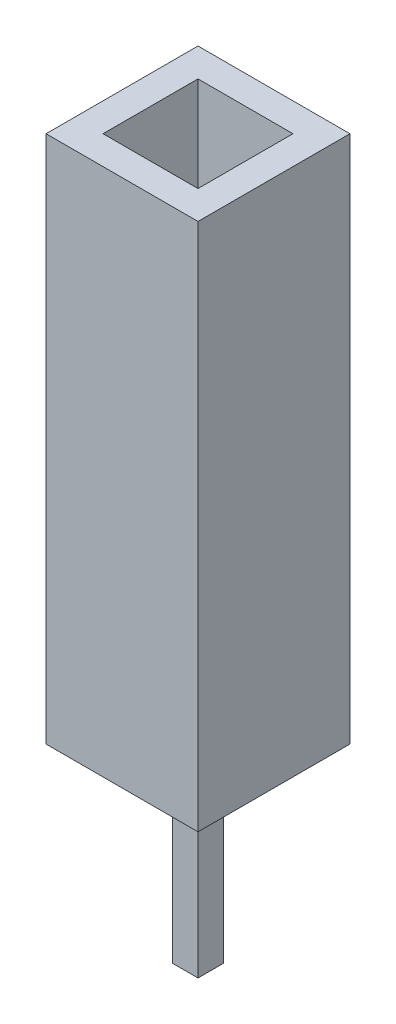
SolidWorks part; units mm, degrees
ref_plane "Front Plane" through (0, 0, 0) normal (0, 0, 1) x (1, 0, 0)
ref_plane "Top Plane" through (0, 0, 0) normal (0, 1, 0) x (1, 0, 0)
ref_plane "Right Plane" through (0, 0, 0) normal (1, 0, 0) x (0, 0, -1)
sketch "Sketch1" plane through (0, 0, 0) normal (0, 1, 0) x (1, 0, 0)
  line L1 (1.2, 1.2) -> (-1.2, 1.2)
  line L2 (1.2, 1.2) -> (1.2, -1.2)
  line L3 (1.2, -1.2) -> (-1.2, -1.2)
  line L4 (-1.2, 1.2) -> (-1.2, -1.2)
  line L5 (1.2, 1.2) -> (-1.2, -1.2) construction
  line L6 (1.2, -1.2) -> (-1.2, 1.2) construction
  point P0 (0, 0)
  dimension "D1" = 2.4
  dimension "D2" = 2.4
extrude "Boss-Extrude1" add sketch "Sketch1" along normal blind 8.35
sketch "Sketch2" plane through (0, 8.35, 0) normal (0, 1, 0) x (1, 0, 0)
  line L1 (-0.75, -0.75) -> (0.75, -0.75)
  line L2 (-0.75, -0.75) -> (-0.75, 0.75)
  line L3 (-0.75, 0.75) -> (0.75, 0.75)
  line L4 (0.75, -0.75) -> (0.75, 0.75)
  line L5 (-0.75, -0.75) -> (0.75, 0.75) construction
  line L6 (-0.75, 0.75) -> (0.75, -0.75) construction
  point P0 (0, 0)
  dimension "D1" = 1.5
  dimension "D2" = 1.5
extrude "Cut-Extrude1" cut sketch "Sketch2" against normal blind 8
sketch "Sketch3" plane through (0, 0, 0) normal (0, -1, 0) x (1, 0, 0)
  line L1 (-0.2, 0.2) -> (0.2, 0.2)
  line L2 (-0.2, 0.2) -> (-0.2, -0.2)
  line L3 (-0.2, -0.2) -> (0.2, -0.2)
  line L4 (0.2, 0.2) -> (0.2, -0.2)
  line L5 (-0.2, 0.2) -> (0.2, -0.2) construction
  line L6 (-0.2, -0.2) -> (0.2, 0.2) construction
  point P0 (0, 0)
  dimension "D1" = 0.4
  dimension "D2" = 0.4
extrude "Boss-Extrude2" add sketch "Sketch3" along normal blind 3
